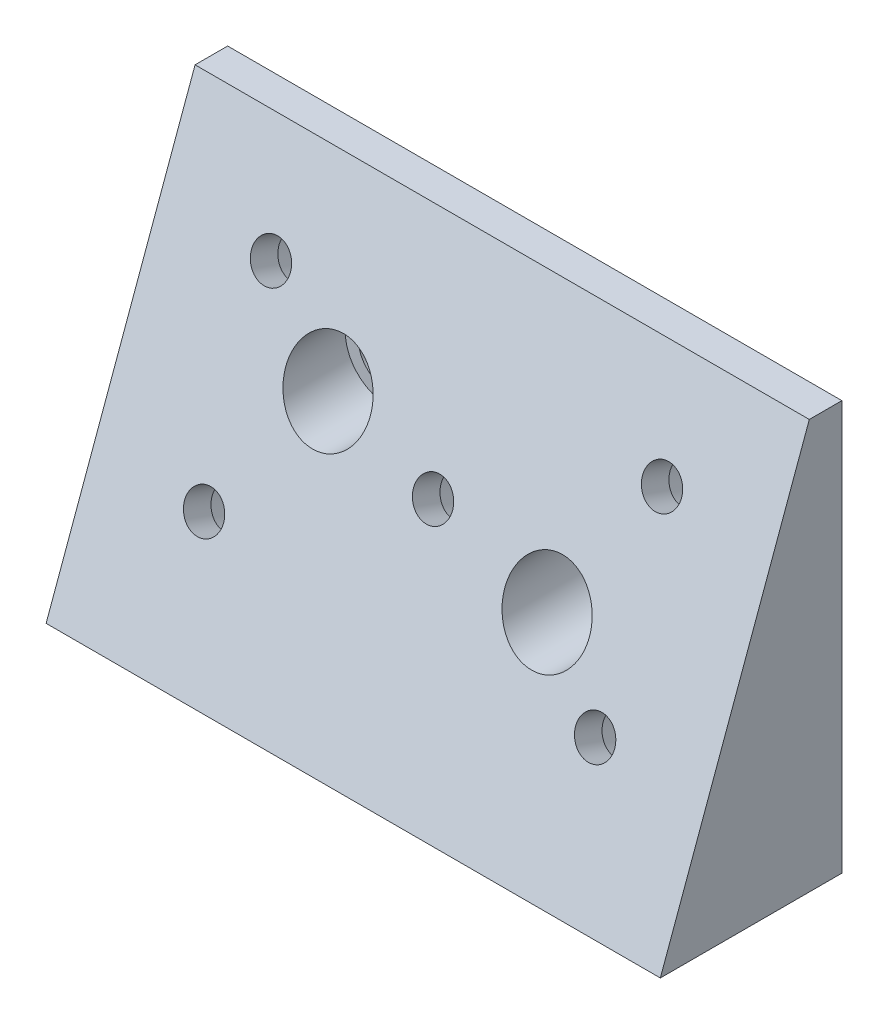
SolidWorks part; units mm, degrees
ref_plane "Front" through (0, 0, 0) normal (0, 0, 1) x (1, 0, 0)
ref_plane "Top" through (0, 0, 0) normal (0, 1, 0) x (1, 0, 0)
ref_plane "Right" through (0, 0, 0) normal (1, 0, 0) x (0, 0, -1)
sketch "Sketch1" plane through (0, 0, 0) normal (1, 0, 0) x (0, 0, -1)
  line L0 (0, 0) -> (0, 62.7897)
  line L1 (0, 62.7897) -> (-5, 62.7897)
  line L2 (0, 0) -> (-27.8536, 0)
  line L3 (-27.8536, 0) -> (-5, 62.7897)
extrude "Boss-Extrude1" add sketch "Sketch1" against normal blind 94.24
sketch "Sketch2" plane through (0, 0, 0) normal (0, 0, -1) x (-1, 0, 0)
  circle A0 centre (28.0218, 29.2508) radius 4.5
  circle A1 centre (28.0218, 29.2508) radius 6.5
  circle A2 centre (64.9901, 38.468) radius 4.5
  circle A3 centre (64.9901, 38.468) radius 6.5
extrude "Cut-Extrude1" cut sketch "Sketch2" against normal blind 94.24 contours A0 | A2
extrude "Cut-Extrude2" cut sketch "Sketch2<3>" against normal blind 94.24 from offset 4.69 contours A1 | A3 offset against normal yes
sketch "Sketch2<3>" plane through (0, 0, 0) normal (0, 0, -1) x (-1, 0, 0) same geometry as "Sketch2"
sketch "Sketch3" plane through (0, 8.952, 24.5953) normal (0, 0.342, 0.9397) x (1, 0, 0)
  circle A0 centre (-17.2009, 11.5175) radius 3
  circle A1 centre (-17.2009, 41.5175) radius 3
  circle A2 centre (-47.2009, 26.5175) radius 3
  circle A3 centre (-77.2009, 41.5175) radius 3
  circle A4 centre (-77.2009, 11.5175) radius 3
  circle A5 centre (-17.2009, 11.5175) radius 4.75
  circle A6 centre (-17.2009, 41.5175) radius 4.75
  circle A7 centre (-47.2009, 26.5175) radius 4.75
  circle A8 centre (-77.2009, 11.5175) radius 4.75
  circle A9 centre (-77.2009, 41.5175) radius 4.75
extrude "Cut-Extrude3" cut sketch "Sketch3" against normal blind 94.24 contours A2 | A3 | A4 | A1 | A0
extrude "Cut-Extrude4" cut sketch "Sketch3<3>" against normal blind 94.24 from offset 4.5 contours A8 | A9 | A7 | A5 | A6 offset against normal yes
sketch "Sketch3<3>" plane through (0, 8.952, 24.5953) normal (0, 0.342, 0.9397) x (1, 0, 0) same geometry as "Sketch3"
